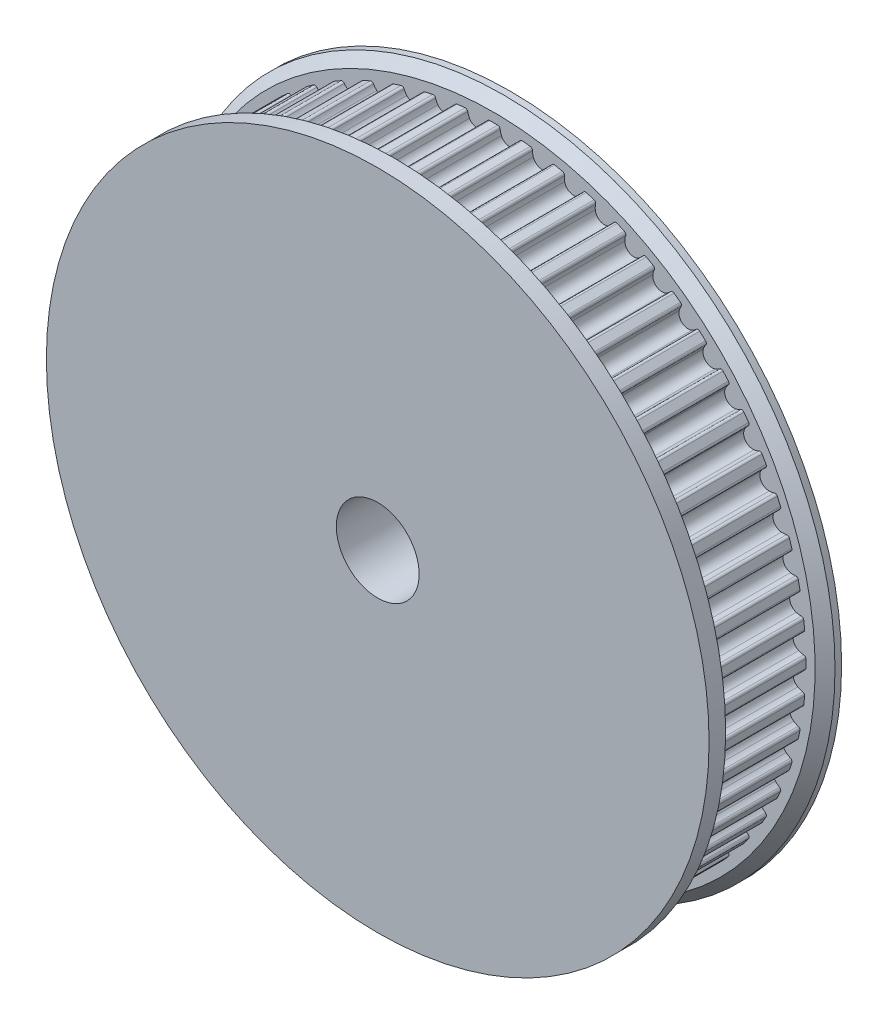
SolidWorks part; units mm, degrees
ref_plane "Front Plane" through (0, 0, 0) normal (0, 0, 1) x (1, 0, 0)
ref_plane "Top Plane" through (0, 0, 0) normal (0, 1, 0) x (1, 0, 0)
ref_plane "Right Plane" through (0, 0, 0) normal (1, 0, 0) x (0, 0, -1)
sketch "Sketch1" plane through (0, 0, 0) normal (0, 0, 1) x (1, 0, 0)
  line L0 (0, 0) -> (0, 19.0986) construction
  line L1 (0, 18.8446) -> (0.2403, 18.8446)
  line L2 (0, 0) -> (0.976, 18.624) construction
  line L3 (0.976, 18.624) -> (0.9995, 19.0724) construction
  line L4 (1.9698, 18.7414) -> (1.7308, 18.7665)
  line L5 (1.9698, 18.7414) -> (2.2088, 18.7162)
  line L6 (3.918, 18.4328) -> (3.6829, 18.4828)
  line L7 (3.918, 18.4328) -> (4.1531, 18.3828)
  line L8 (5.8233, 17.9223) -> (5.5947, 17.9965)
  line L9 (5.8233, 17.9223) -> (6.0519, 17.848)
  line L10 (7.6648, 17.2154) -> (7.4452, 17.3131)
  line L11 (7.6648, 17.2154) -> (7.8844, 17.1176)
  line L12 (9.4223, 16.3199) -> (9.2142, 16.4401)
  line L13 (9.4223, 16.3199) -> (9.6304, 16.1997)
  line L14 (11.0766, 15.2456) -> (10.8821, 15.3869)
  line L15 (11.0766, 15.2456) -> (11.271, 15.1043)
  line L16 (12.6095, 14.0043) -> (12.4309, 14.1651)
  line L17 (12.6095, 14.0043) -> (12.7881, 13.8434)
  line L18 (14.0043, 12.6095) -> (13.8434, 12.7881)
  line L19 (14.0043, 12.6095) -> (14.1651, 12.4309)
  line L20 (15.2456, 11.0766) -> (15.1043, 11.271)
  line L21 (15.2456, 11.0766) -> (15.3869, 10.8821)
  line L22 (16.3199, 9.4223) -> (16.1997, 9.6304)
  line L23 (16.3199, 9.4223) -> (16.4401, 9.2142)
  line L24 (17.2154, 7.6648) -> (17.1176, 7.8844)
  line L25 (17.2154, 7.6648) -> (17.3131, 7.4452)
  line L26 (17.9223, 5.8233) -> (17.848, 6.0519)
  line L27 (17.9223, 5.8233) -> (17.9965, 5.5947)
  line L28 (18.4328, 3.918) -> (18.3828, 4.1531)
  line L29 (18.4328, 3.918) -> (18.4828, 3.6829)
  line L30 (18.7414, 1.9698) -> (18.7162, 2.2088)
  line L31 (18.7414, 1.9698) -> (18.7665, 1.7308)
  line L32 (18.8446, 0) -> (18.8446, 0.2403)
  line L33 (18.8446, 0) -> (18.8446, -0.2403)
  line L34 (18.7414, -1.9698) -> (18.7665, -1.7308)
  line L35 (18.7414, -1.9698) -> (18.7162, -2.2088)
  line L36 (18.4328, -3.918) -> (18.4828, -3.6829)
  line L37 (18.4328, -3.918) -> (18.3828, -4.1531)
  line L38 (17.9223, -5.8233) -> (17.9965, -5.5947)
  line L39 (17.9223, -5.8233) -> (17.848, -6.0519)
  line L40 (17.2154, -7.6648) -> (17.3131, -7.4452)
  line L41 (17.2154, -7.6648) -> (17.1176, -7.8844)
  line L42 (16.3199, -9.4223) -> (16.4401, -9.2142)
  line L43 (16.3199, -9.4223) -> (16.1997, -9.6304)
  line L44 (15.2456, -11.0766) -> (15.3869, -10.8821)
  line L45 (15.2456, -11.0766) -> (15.1043, -11.271)
  line L46 (14.0043, -12.6095) -> (14.1651, -12.4309)
  line L47 (14.0043, -12.6095) -> (13.8434, -12.7881)
  line L48 (12.6095, -14.0043) -> (12.7881, -13.8434)
  line L49 (12.6095, -14.0043) -> (12.4309, -14.1651)
  line L50 (11.0766, -15.2456) -> (11.271, -15.1043)
  line L51 (11.0766, -15.2456) -> (10.8821, -15.3869)
  line L52 (9.4223, -16.3199) -> (9.6304, -16.1997)
  line L53 (9.4223, -16.3199) -> (9.2142, -16.4401)
  line L54 (7.6648, -17.2154) -> (7.8844, -17.1176)
  line L55 (7.6648, -17.2154) -> (7.4452, -17.3131)
  line L56 (5.8233, -17.9223) -> (6.0519, -17.848)
  line L57 (5.8233, -17.9223) -> (5.5947, -17.9965)
  line L58 (3.918, -18.4328) -> (4.1531, -18.3828)
  line L59 (3.918, -18.4328) -> (3.6829, -18.4828)
  line L60 (1.9698, -18.7414) -> (2.2088, -18.7162)
  line L61 (1.9698, -18.7414) -> (1.7308, -18.7665)
  line L62 (0, -18.8446) -> (0.2403, -18.8446)
  line L63 (0, -18.8446) -> (-0.2403, -18.8446)
  line L64 (-1.9698, -18.7414) -> (-1.7308, -18.7665)
  line L65 (-1.9698, -18.7414) -> (-2.2088, -18.7162)
  line L66 (-3.918, -18.4328) -> (-3.6829, -18.4828)
  line L67 (-3.918, -18.4328) -> (-4.1531, -18.3828)
  line L68 (-5.8233, -17.9223) -> (-5.5947, -17.9965)
  line L69 (-5.8233, -17.9223) -> (-6.0519, -17.848)
  line L70 (-7.6648, -17.2154) -> (-7.4452, -17.3131)
  line L71 (-7.6648, -17.2154) -> (-7.8844, -17.1176)
  line L72 (-9.4223, -16.3199) -> (-9.2142, -16.4401)
  line L73 (-9.4223, -16.3199) -> (-9.6304, -16.1997)
  line L74 (-11.0766, -15.2456) -> (-10.8821, -15.3869)
  line L75 (-11.0766, -15.2456) -> (-11.271, -15.1043)
  line L76 (-12.6095, -14.0043) -> (-12.4309, -14.1651)
  line L77 (-12.6095, -14.0043) -> (-12.7881, -13.8434)
  line L78 (-14.0043, -12.6095) -> (-13.8434, -12.7881)
  line L79 (-14.0043, -12.6095) -> (-14.1651, -12.4309)
  line L80 (-15.2456, -11.0766) -> (-15.1043, -11.271)
  line L81 (-15.2456, -11.0766) -> (-15.3869, -10.8821)
  line L82 (-16.3199, -9.4223) -> (-16.1997, -9.6304)
  line L83 (-16.3199, -9.4223) -> (-16.4401, -9.2142)
  line L84 (-17.2154, -7.6648) -> (-17.1176, -7.8844)
  line L85 (-17.2154, -7.6648) -> (-17.3131, -7.4452)
  line L86 (-17.9223, -5.8233) -> (-17.848, -6.0519)
  line L87 (-17.9223, -5.8233) -> (-17.9965, -5.5947)
  line L88 (-18.4328, -3.918) -> (-18.3828, -4.1531)
  line L89 (-18.4328, -3.918) -> (-18.4828, -3.6829)
  line L90 (-18.7414, -1.9698) -> (-18.7162, -2.2088)
  line L91 (-18.7414, -1.9698) -> (-18.7665, -1.7308)
  line L92 (-18.8446, 0) -> (-18.8446, -0.2403)
  line L93 (-18.8446, 0) -> (-18.8446, 0.2403)
  line L94 (-18.7414, 1.9698) -> (-18.7665, 1.7308)
  line L95 (-18.7414, 1.9698) -> (-18.7162, 2.2088)
  line L96 (-18.4328, 3.918) -> (-18.4828, 3.6829)
  line L97 (-18.4328, 3.918) -> (-18.3828, 4.1531)
  line L98 (-17.9223, 5.8233) -> (-17.9965, 5.5947)
  line L99 (-17.9223, 5.8233) -> (-17.848, 6.0519)
  line L100 (-17.2154, 7.6648) -> (-17.3131, 7.4452)
  line L101 (-17.2154, 7.6648) -> (-17.1176, 7.8844)
  line L102 (-16.3199, 9.4223) -> (-16.4401, 9.2142)
  line L103 (-16.3199, 9.4223) -> (-16.1997, 9.6304)
  line L104 (-15.2456, 11.0766) -> (-15.3869, 10.8821)
  line L105 (-15.2456, 11.0766) -> (-15.1043, 11.271)
  line L106 (-14.0043, 12.6095) -> (-14.1651, 12.4309)
  line L107 (-14.0043, 12.6095) -> (-13.8434, 12.7881)
  line L108 (-12.6095, 14.0043) -> (-12.7881, 13.8434)
  line L109 (-12.6095, 14.0043) -> (-12.4309, 14.1651)
  line L110 (-11.0766, 15.2456) -> (-11.271, 15.1043)
  line L111 (-11.0766, 15.2456) -> (-10.8821, 15.3869)
  line L112 (-9.4223, 16.3199) -> (-9.6304, 16.1997)
  line L113 (-9.4223, 16.3199) -> (-9.2142, 16.4401)
  line L114 (-7.6648, 17.2154) -> (-7.8844, 17.1176)
  line L115 (-7.6648, 17.2154) -> (-7.4452, 17.3131)
  line L116 (-5.8233, 17.9223) -> (-6.0519, 17.848)
  line L117 (-5.8233, 17.9223) -> (-5.5947, 17.9965)
  line L118 (-3.918, 18.4328) -> (-4.1531, 18.3828)
  line L119 (-3.918, 18.4328) -> (-3.6829, 18.4828)
  line L120 (-1.9698, 18.7414) -> (-2.2088, 18.7162)
  line L121 (-1.9698, 18.7414) -> (-1.7308, 18.7665)
  line L122 (0, 18.8446) -> (-0.2403, 18.8446)
  line L123 (0, 0) -> (1.4615, 18.3551) construction
  circle A0 centre (0, 0) radius 19.0986 construction
  arc A1 (0.2403, 18.8446) -> (0.3897, 18.7081) centre (0.2403, 18.6946) cw
  arc A2 (0.3897, 18.7081) -> (0.4651, 18.4073) centre (1.3857, 18.7978) ccw
  arc A3 (0.4651, 18.4073) -> (1.4615, 18.3551) centre (0.976, 18.624) ccw
  arc A4 (1.5679, 18.6463) -> (1.4615, 18.3551) centre (0.5868, 18.8397) cw
  arc A5 (1.7308, 18.7665) -> (1.5679, 18.6463) centre (1.7151, 18.6173) ccw
  arc A6 (2.2088, 18.7162) -> (2.3431, 18.5648) centre (2.1931, 18.5671) cw
  arc A7 (2.3431, 18.5648) -> (2.3867, 18.2578) centre (3.343, 18.55) ccw
  arc A8 (2.3867, 18.2578) -> (3.3721, 18.1017) centre (2.9174, 18.42) ccw
  arc A9 (3.5084, 18.3803) -> (3.3721, 18.1017) centre (2.5529, 18.6752) cw
  arc A10 (3.6829, 18.4828) -> (3.5084, 18.3803) centre (3.6517, 18.336) ccw
  arc A11 (4.1531, 18.3828) -> (4.2708, 18.2182) centre (4.1219, 18.2361) cw
  arc A12 (4.2708, 18.2182) -> (4.282, 17.9083) centre (5.2637, 18.099) ccw
  arc A13 (4.282, 17.9083) -> (5.2458, 17.6501) centre (4.8269, 18.0141) ccw
  arc A14 (5.4104, 17.9129) -> (5.2458, 17.6501) centre (4.491, 18.306) cw
  arc A15 (5.5947, 17.9965) -> (5.4104, 17.9129) centre (5.5484, 17.8539) ccw
  arc A16 (6.0519, 17.848) -> (6.1518, 17.672) centre (6.0055, 17.7053) cw
  arc A17 (6.1518, 17.672) -> (6.1305, 17.3626) centre (7.1267, 17.4496) ccw
  arc A18 (6.1305, 17.3626) -> (7.062, 17.0051) centre (6.6834, 17.4109) ccw
  arc A19 (7.2532, 17.2492) -> (7.062, 17.0051) centre (6.3799, 17.7363) cw
  arc A20 (7.4452, 17.3131) -> (7.2532, 17.2492) centre (7.3842, 17.1761) ccw
  arc A21 (7.8844, 17.1176) -> (7.9653, 16.9321) centre (7.8233, 16.9806) cw
  arc A22 (7.9653, 16.9321) -> (7.9118, 16.6267) centre (8.9117, 16.6091) ccw
  arc A23 (7.9118, 16.6267) -> (8.8008, 16.1737) centre (8.4667, 16.6169) ccw
  arc A24 (9.0165, 16.3965) -> (8.8008, 16.1737) centre (8.1989, 16.9723) cw
  arc A25 (9.2142, 16.4401) -> (9.0165, 16.3965) centre (9.1392, 16.3102) ccw
  arc A26 (9.6304, 16.1997) -> (9.6916, 16.0068) centre (9.5554, 16.0698) cw
  arc A27 (9.6916, 16.0068) -> (9.6064, 15.7086) centre (10.599, 15.5866) ccw
  arc A28 (9.6064, 15.7086) -> (10.4432, 15.1652) centre (10.1573, 15.6409) ccw
  arc A29 (10.681, 15.3642) -> (10.4432, 15.1652) centre (9.928, 16.0223) cw
  arc A30 (10.8821, 15.3869) -> (10.681, 15.3642) centre (10.794, 15.2655) ccw
  arc A31 (11.271, 15.1043) -> (11.3116, 14.9061) centre (11.1828, 14.983) cw
  arc A32 (11.3116, 14.9061) -> (11.1958, 14.6184) centre (12.1701, 14.3933) ccw
  arc A33 (11.1958, 14.6184) -> (11.9712, 13.9905) centre (11.7366, 14.4935) ccw
  arc A34 (12.2285, 14.1636) -> (11.9712, 13.9905) centre (11.5484, 14.8967) cw
  arc A35 (12.4309, 14.1651) -> (12.2285, 14.1636) centre (12.3305, 14.0536) ccw
  arc A36 (12.7881, 13.8434) -> (12.8078, 13.642) centre (12.6877, 13.732) cw
  arc A37 (12.8078, 13.642) -> (12.6625, 13.368) centre (13.608, 13.0423) ccw
  arc A38 (12.6625, 13.368) -> (13.368, 12.6625) centre (13.1873, 13.1873) ccw
  arc A39 (13.642, 12.8078) -> (13.368, 12.6625) centre (13.0423, 13.608) cw
  arc A40 (13.8434, 12.7881) -> (13.642, 12.8078) centre (13.732, 12.6877) ccw
  arc A41 (14.1651, 12.4309) -> (14.1636, 12.2285) centre (14.0536, 12.3305) cw
  arc A42 (14.1636, 12.2285) -> (13.9905, 11.9712) centre (14.8967, 11.5484) ccw
  arc A43 (13.9905, 11.9712) -> (14.6184, 11.1958) centre (14.4935, 11.7366) ccw
  arc A44 (14.9061, 11.3116) -> (14.6184, 11.1958) centre (14.3933, 12.1701) cw
  arc A45 (15.1043, 11.271) -> (14.9061, 11.3116) centre (14.983, 11.1828) ccw
  arc A46 (15.3869, 10.8821) -> (15.3642, 10.681) centre (15.2655, 10.794) cw
  arc A47 (15.3642, 10.681) -> (15.1652, 10.4432) centre (16.0223, 9.928) ccw
  arc A48 (15.1652, 10.4432) -> (15.7086, 9.6064) centre (15.6409, 10.1573) ccw
  arc A49 (16.0068, 9.6916) -> (15.7086, 9.6064) centre (15.5866, 10.599) cw
  arc A50 (16.1997, 9.6304) -> (16.0068, 9.6916) centre (16.0698, 9.5554) ccw
  arc A51 (16.4401, 9.2142) -> (16.3965, 9.0165) centre (16.3102, 9.1392) cw
  arc A52 (16.3965, 9.0165) -> (16.1737, 8.8008) centre (16.9723, 8.1989) ccw
  arc A53 (16.1737, 8.8008) -> (16.6267, 7.9118) centre (16.6169, 8.4667) ccw
  arc A54 (16.9321, 7.9653) -> (16.6267, 7.9118) centre (16.6091, 8.9117) cw
  arc A55 (17.1176, 7.8844) -> (16.9321, 7.9653) centre (16.9806, 7.8233) ccw
  arc A56 (17.3131, 7.4452) -> (17.2492, 7.2532) centre (17.1761, 7.3842) cw
  arc A57 (17.2492, 7.2532) -> (17.0051, 7.062) centre (17.7363, 6.3799) ccw
  arc A58 (17.0051, 7.062) -> (17.3626, 6.1305) centre (17.4109, 6.6834) ccw
  arc A59 (17.672, 6.1518) -> (17.3626, 6.1305) centre (17.4496, 7.1267) cw
  arc A60 (17.848, 6.0519) -> (17.672, 6.1518) centre (17.7053, 6.0055) ccw
  arc A61 (17.9965, 5.5947) -> (17.9129, 5.4104) centre (17.8539, 5.5484) cw
  arc A62 (17.9129, 5.4104) -> (17.6501, 5.2458) centre (18.306, 4.491) ccw
  arc A63 (17.6501, 5.2458) -> (17.9083, 4.282) centre (18.0141, 4.8269) ccw
  arc A64 (18.2182, 4.2708) -> (17.9083, 4.282) centre (18.099, 5.2637) cw
  arc A65 (18.3828, 4.1531) -> (18.2182, 4.2708) centre (18.2361, 4.1219) ccw
  arc A66 (18.4828, 3.6829) -> (18.3803, 3.5084) centre (18.336, 3.6517) cw
  arc A67 (18.3803, 3.5084) -> (18.1017, 3.3721) centre (18.6752, 2.5529) ccw
  arc A68 (18.1017, 3.3721) -> (18.2578, 2.3867) centre (18.42, 2.9174) ccw
  arc A69 (18.5648, 2.3431) -> (18.2578, 2.3867) centre (18.55, 3.343) cw
  arc A70 (18.7162, 2.2088) -> (18.5648, 2.3431) centre (18.5671, 2.1931) ccw
  arc A71 (18.7665, 1.7308) -> (18.6463, 1.5679) centre (18.6173, 1.7151) cw
  arc A72 (18.6463, 1.5679) -> (18.3551, 1.4615) centre (18.8397, 0.5868) ccw
  arc A73 (18.3551, 1.4615) -> (18.4073, 0.4651) centre (18.624, 0.976) ccw
  arc A74 (18.7081, 0.3897) -> (18.4073, 0.4651) centre (18.7978, 1.3857) cw
  arc A75 (18.8446, 0.2403) -> (18.7081, 0.3897) centre (18.6946, 0.2403) ccw
  arc A76 (18.8446, -0.2403) -> (18.7081, -0.3897) centre (18.6946, -0.2403) cw
  arc A77 (18.7081, -0.3897) -> (18.4073, -0.4651) centre (18.7978, -1.3857) ccw
  arc A78 (18.4073, -0.4651) -> (18.3551, -1.4615) centre (18.624, -0.976) ccw
  arc A79 (18.6463, -1.5679) -> (18.3551, -1.4615) centre (18.8397, -0.5868) cw
  arc A80 (18.7665, -1.7308) -> (18.6463, -1.5679) centre (18.6173, -1.7151) ccw
  arc A81 (18.7162, -2.2088) -> (18.5648, -2.3431) centre (18.5671, -2.1931) cw
  arc A82 (18.5648, -2.3431) -> (18.2578, -2.3867) centre (18.55, -3.343) ccw
  arc A83 (18.2578, -2.3867) -> (18.1017, -3.3721) centre (18.42, -2.9174) ccw
  arc A84 (18.3803, -3.5084) -> (18.1017, -3.3721) centre (18.6752, -2.5529) cw
  arc A85 (18.4828, -3.6829) -> (18.3803, -3.5084) centre (18.336, -3.6517) ccw
  arc A86 (18.3828, -4.1531) -> (18.2182, -4.2708) centre (18.2361, -4.1219) cw
  arc A87 (18.2182, -4.2708) -> (17.9083, -4.282) centre (18.099, -5.2637) ccw
  arc A88 (17.9083, -4.282) -> (17.6501, -5.2458) centre (18.0141, -4.8269) ccw
  arc A89 (17.9129, -5.4104) -> (17.6501, -5.2458) centre (18.306, -4.491) cw
  arc A90 (17.9965, -5.5947) -> (17.9129, -5.4104) centre (17.8539, -5.5484) ccw
  arc A91 (17.848, -6.0519) -> (17.672, -6.1518) centre (17.7053, -6.0055) cw
  arc A92 (17.672, -6.1518) -> (17.3626, -6.1305) centre (17.4496, -7.1267) ccw
  arc A93 (17.3626, -6.1305) -> (17.0051, -7.062) centre (17.4109, -6.6834) ccw
  arc A94 (17.2492, -7.2532) -> (17.0051, -7.062) centre (17.7363, -6.3799) cw
  arc A95 (17.3131, -7.4452) -> (17.2492, -7.2532) centre (17.1761, -7.3842) ccw
  arc A96 (17.1176, -7.8844) -> (16.9321, -7.9653) centre (16.9806, -7.8233) cw
  arc A97 (16.9321, -7.9653) -> (16.6267, -7.9118) centre (16.6091, -8.9117) ccw
  arc A98 (16.6267, -7.9118) -> (16.1737, -8.8008) centre (16.6169, -8.4667) ccw
  arc A99 (16.3965, -9.0165) -> (16.1737, -8.8008) centre (16.9723, -8.1989) cw
  arc A100 (16.4401, -9.2142) -> (16.3965, -9.0165) centre (16.3102, -9.1392) ccw
  arc A101 (16.1997, -9.6304) -> (16.0068, -9.6916) centre (16.0698, -9.5554) cw
  arc A102 (16.0068, -9.6916) -> (15.7086, -9.6064) centre (15.5866, -10.599) ccw
  arc A103 (15.7086, -9.6064) -> (15.1652, -10.4432) centre (15.6409, -10.1573) ccw
  arc A104 (15.3642, -10.681) -> (15.1652, -10.4432) centre (16.0223, -9.928) cw
  arc A105 (15.3869, -10.8821) -> (15.3642, -10.681) centre (15.2655, -10.794) ccw
  arc A106 (15.1043, -11.271) -> (14.9061, -11.3116) centre (14.983, -11.1828) cw
  arc A107 (14.9061, -11.3116) -> (14.6184, -11.1958) centre (14.3933, -12.1701) ccw
  arc A108 (14.6184, -11.1958) -> (13.9905, -11.9712) centre (14.4935, -11.7366) ccw
  arc A109 (14.1636, -12.2285) -> (13.9905, -11.9712) centre (14.8967, -11.5484) cw
  arc A110 (14.1651, -12.4309) -> (14.1636, -12.2285) centre (14.0536, -12.3305) ccw
  arc A111 (13.8434, -12.7881) -> (13.642, -12.8078) centre (13.732, -12.6877) cw
  arc A112 (13.642, -12.8078) -> (13.368, -12.6625) centre (13.0423, -13.608) ccw
  arc A113 (13.368, -12.6625) -> (12.6625, -13.368) centre (13.1873, -13.1873) ccw
  arc A114 (12.8078, -13.642) -> (12.6625, -13.368) centre (13.608, -13.0423) cw
  arc A115 (12.7881, -13.8434) -> (12.8078, -13.642) centre (12.6877, -13.732) ccw
  arc A116 (12.4309, -14.1651) -> (12.2285, -14.1636) centre (12.3305, -14.0536) cw
  arc A117 (12.2285, -14.1636) -> (11.9712, -13.9905) centre (11.5484, -14.8967) ccw
  arc A118 (11.9712, -13.9905) -> (11.1958, -14.6184) centre (11.7366, -14.4935) ccw
  arc A119 (11.3116, -14.9061) -> (11.1958, -14.6184) centre (12.1701, -14.3933) cw
  arc A120 (11.271, -15.1043) -> (11.3116, -14.9061) centre (11.1828, -14.983) ccw
  arc A121 (10.8821, -15.3869) -> (10.681, -15.3642) centre (10.794, -15.2655) cw
  arc A122 (10.681, -15.3642) -> (10.4432, -15.1652) centre (9.928, -16.0223) ccw
  arc A123 (10.4432, -15.1652) -> (9.6064, -15.7086) centre (10.1573, -15.6409) ccw
  arc A124 (9.6916, -16.0068) -> (9.6064, -15.7086) centre (10.599, -15.5866) cw
  arc A125 (9.6304, -16.1997) -> (9.6916, -16.0068) centre (9.5554, -16.0698) ccw
  arc A126 (9.2142, -16.4401) -> (9.0165, -16.3965) centre (9.1392, -16.3102) cw
  arc A127 (9.0165, -16.3965) -> (8.8008, -16.1737) centre (8.1989, -16.9723) ccw
  arc A128 (8.8008, -16.1737) -> (7.9118, -16.6267) centre (8.4667, -16.6169) ccw
  arc A129 (7.9653, -16.9321) -> (7.9118, -16.6267) centre (8.9117, -16.6091) cw
  arc A130 (7.8844, -17.1176) -> (7.9653, -16.9321) centre (7.8233, -16.9806) ccw
  arc A131 (7.4452, -17.3131) -> (7.2532, -17.2492) centre (7.3842, -17.1761) cw
  arc A132 (7.2532, -17.2492) -> (7.062, -17.0051) centre (6.3799, -17.7363) ccw
  arc A133 (7.062, -17.0051) -> (6.1305, -17.3626) centre (6.6834, -17.4109) ccw
  arc A134 (6.1518, -17.672) -> (6.1305, -17.3626) centre (7.1267, -17.4496) cw
  arc A135 (6.0519, -17.848) -> (6.1518, -17.672) centre (6.0055, -17.7053) ccw
  arc A136 (5.5947, -17.9965) -> (5.4104, -17.9129) centre (5.5484, -17.8539) cw
  arc A137 (5.4104, -17.9129) -> (5.2458, -17.6501) centre (4.491, -18.306) ccw
  arc A138 (5.2458, -17.6501) -> (4.282, -17.9083) centre (4.8269, -18.0141) ccw
  arc A139 (4.2708, -18.2182) -> (4.282, -17.9083) centre (5.2637, -18.099) cw
  arc A140 (4.1531, -18.3828) -> (4.2708, -18.2182) centre (4.1219, -18.2361) ccw
  arc A141 (3.6829, -18.4828) -> (3.5084, -18.3803) centre (3.6517, -18.336) cw
  arc A142 (3.5084, -18.3803) -> (3.3721, -18.1017) centre (2.5529, -18.6752) ccw
  arc A143 (3.3721, -18.1017) -> (2.3867, -18.2578) centre (2.9174, -18.42) ccw
  arc A144 (2.3431, -18.5648) -> (2.3867, -18.2578) centre (3.343, -18.55) cw
  arc A145 (2.2088, -18.7162) -> (2.3431, -18.5648) centre (2.1931, -18.5671) ccw
  arc A146 (1.7308, -18.7665) -> (1.5679, -18.6463) centre (1.7151, -18.6173) cw
  arc A147 (1.5679, -18.6463) -> (1.4615, -18.3551) centre (0.5868, -18.8397) ccw
  arc A148 (1.4615, -18.3551) -> (0.4651, -18.4073) centre (0.976, -18.624) ccw
  arc A149 (0.3897, -18.7081) -> (0.4651, -18.4073) centre (1.3857, -18.7978) cw
  arc A150 (0.2403, -18.8446) -> (0.3897, -18.7081) centre (0.2403, -18.6946) ccw
  arc A151 (-0.2403, -18.8446) -> (-0.3897, -18.7081) centre (-0.2403, -18.6946) cw
  arc A152 (-0.3897, -18.7081) -> (-0.4651, -18.4073) centre (-1.3857, -18.7978) ccw
  arc A153 (-0.4651, -18.4073) -> (-1.4615, -18.3551) centre (-0.976, -18.624) ccw
  arc A154 (-1.5679, -18.6463) -> (-1.4615, -18.3551) centre (-0.5868, -18.8397) cw
  arc A155 (-1.7308, -18.7665) -> (-1.5679, -18.6463) centre (-1.7151, -18.6173) ccw
  arc A156 (-2.2088, -18.7162) -> (-2.3431, -18.5648) centre (-2.1931, -18.5671) cw
  arc A157 (-2.3431, -18.5648) -> (-2.3867, -18.2578) centre (-3.343, -18.55) ccw
  arc A158 (-2.3867, -18.2578) -> (-3.3721, -18.1017) centre (-2.9174, -18.42) ccw
  arc A159 (-3.5084, -18.3803) -> (-3.3721, -18.1017) centre (-2.5529, -18.6752) cw
  arc A160 (-3.6829, -18.4828) -> (-3.5084, -18.3803) centre (-3.6517, -18.336) ccw
  arc A161 (-4.1531, -18.3828) -> (-4.2708, -18.2182) centre (-4.1219, -18.2361) cw
  arc A162 (-4.2708, -18.2182) -> (-4.282, -17.9083) centre (-5.2637, -18.099) ccw
  arc A163 (-4.282, -17.9083) -> (-5.2458, -17.6501) centre (-4.8269, -18.0141) ccw
  arc A164 (-5.4104, -17.9129) -> (-5.2458, -17.6501) centre (-4.491, -18.306) cw
  arc A165 (-5.5947, -17.9965) -> (-5.4104, -17.9129) centre (-5.5484, -17.8539) ccw
  arc A166 (-6.0519, -17.848) -> (-6.1518, -17.672) centre (-6.0055, -17.7053) cw
  arc A167 (-6.1518, -17.672) -> (-6.1305, -17.3626) centre (-7.1267, -17.4496) ccw
  arc A168 (-6.1305, -17.3626) -> (-7.062, -17.0051) centre (-6.6834, -17.4109) ccw
  arc A169 (-7.2532, -17.2492) -> (-7.062, -17.0051) centre (-6.3799, -17.7363) cw
  arc A170 (-7.4452, -17.3131) -> (-7.2532, -17.2492) centre (-7.3842, -17.1761) ccw
  arc A171 (-7.8844, -17.1176) -> (-7.9653, -16.9321) centre (-7.8233, -16.9806) cw
  arc A172 (-7.9653, -16.9321) -> (-7.9118, -16.6267) centre (-8.9117, -16.6091) ccw
  arc A173 (-7.9118, -16.6267) -> (-8.8008, -16.1737) centre (-8.4667, -16.6169) ccw
  arc A174 (-9.0165, -16.3965) -> (-8.8008, -16.1737) centre (-8.1989, -16.9723) cw
  arc A175 (-9.2142, -16.4401) -> (-9.0165, -16.3965) centre (-9.1392, -16.3102) ccw
  arc A176 (-9.6304, -16.1997) -> (-9.6916, -16.0068) centre (-9.5554, -16.0698) cw
  arc A177 (-9.6916, -16.0068) -> (-9.6064, -15.7086) centre (-10.599, -15.5866) ccw
  arc A178 (-9.6064, -15.7086) -> (-10.4432, -15.1652) centre (-10.1573, -15.6409) ccw
  arc A179 (-10.681, -15.3642) -> (-10.4432, -15.1652) centre (-9.928, -16.0223) cw
  arc A180 (-10.8821, -15.3869) -> (-10.681, -15.3642) centre (-10.794, -15.2655) ccw
  arc A181 (-11.271, -15.1043) -> (-11.3116, -14.9061) centre (-11.1828, -14.983) cw
  arc A182 (-11.3116, -14.9061) -> (-11.1958, -14.6184) centre (-12.1701, -14.3933) ccw
  arc A183 (-11.1958, -14.6184) -> (-11.9712, -13.9905) centre (-11.7366, -14.4935) ccw
  arc A184 (-12.2285, -14.1636) -> (-11.9712, -13.9905) centre (-11.5484, -14.8967) cw
  arc A185 (-12.4309, -14.1651) -> (-12.2285, -14.1636) centre (-12.3305, -14.0536) ccw
  arc A186 (-12.7881, -13.8434) -> (-12.8078, -13.642) centre (-12.6877, -13.732) cw
  arc A187 (-12.8078, -13.642) -> (-12.6625, -13.368) centre (-13.608, -13.0423) ccw
  arc A188 (-12.6625, -13.368) -> (-13.368, -12.6625) centre (-13.1873, -13.1873) ccw
  arc A189 (-13.642, -12.8078) -> (-13.368, -12.6625) centre (-13.0423, -13.608) cw
  arc A190 (-13.8434, -12.7881) -> (-13.642, -12.8078) centre (-13.732, -12.6877) ccw
  arc A191 (-14.1651, -12.4309) -> (-14.1636, -12.2285) centre (-14.0536, -12.3305) cw
  arc A192 (-14.1636, -12.2285) -> (-13.9905, -11.9712) centre (-14.8967, -11.5484) ccw
  arc A193 (-13.9905, -11.9712) -> (-14.6184, -11.1958) centre (-14.4935, -11.7366) ccw
  arc A194 (-14.9061, -11.3116) -> (-14.6184, -11.1958) centre (-14.3933, -12.1701) cw
  arc A195 (-15.1043, -11.271) -> (-14.9061, -11.3116) centre (-14.983, -11.1828) ccw
  arc A196 (-15.3869, -10.8821) -> (-15.3642, -10.681) centre (-15.2655, -10.794) cw
  arc A197 (-15.3642, -10.681) -> (-15.1652, -10.4432) centre (-16.0223, -9.928) ccw
  arc A198 (-15.1652, -10.4432) -> (-15.7086, -9.6064) centre (-15.6409, -10.1573) ccw
  arc A199 (-16.0068, -9.6916) -> (-15.7086, -9.6064) centre (-15.5866, -10.599) cw
  arc A200 (-16.1997, -9.6304) -> (-16.0068, -9.6916) centre (-16.0698, -9.5554) ccw
  arc A201 (-16.4401, -9.2142) -> (-16.3965, -9.0165) centre (-16.3102, -9.1392) cw
  arc A202 (-16.3965, -9.0165) -> (-16.1737, -8.8008) centre (-16.9723, -8.1989) ccw
  arc A203 (-16.1737, -8.8008) -> (-16.6267, -7.9118) centre (-16.6169, -8.4667) ccw
  arc A204 (-16.9321, -7.9653) -> (-16.6267, -7.9118) centre (-16.6091, -8.9117) cw
  arc A205 (-17.1176, -7.8844) -> (-16.9321, -7.9653) centre (-16.9806, -7.8233) ccw
  arc A206 (-17.3131, -7.4452) -> (-17.2492, -7.2532) centre (-17.1761, -7.3842) cw
  arc A207 (-17.2492, -7.2532) -> (-17.0051, -7.062) centre (-17.7363, -6.3799) ccw
  arc A208 (-17.0051, -7.062) -> (-17.3626, -6.1305) centre (-17.4109, -6.6834) ccw
  arc A209 (-17.672, -6.1518) -> (-17.3626, -6.1305) centre (-17.4496, -7.1267) cw
  arc A210 (-17.848, -6.0519) -> (-17.672, -6.1518) centre (-17.7053, -6.0055) ccw
  arc A211 (-17.9965, -5.5947) -> (-17.9129, -5.4104) centre (-17.8539, -5.5484) cw
  arc A212 (-17.9129, -5.4104) -> (-17.6501, -5.2458) centre (-18.306, -4.491) ccw
  arc A213 (-17.6501, -5.2458) -> (-17.9083, -4.282) centre (-18.0141, -4.8269) ccw
  arc A214 (-18.2182, -4.2708) -> (-17.9083, -4.282) centre (-18.099, -5.2637) cw
  arc A215 (-18.3828, -4.1531) -> (-18.2182, -4.2708) centre (-18.2361, -4.1219) ccw
  arc A216 (-18.4828, -3.6829) -> (-18.3803, -3.5084) centre (-18.336, -3.6517) cw
  arc A217 (-18.3803, -3.5084) -> (-18.1017, -3.3721) centre (-18.6752, -2.5529) ccw
  arc A218 (-18.1017, -3.3721) -> (-18.2578, -2.3867) centre (-18.42, -2.9174) ccw
  arc A219 (-18.5648, -2.3431) -> (-18.2578, -2.3867) centre (-18.55, -3.343) cw
  arc A220 (-18.7162, -2.2088) -> (-18.5648, -2.3431) centre (-18.5671, -2.1931) ccw
  arc A221 (-18.7665, -1.7308) -> (-18.6463, -1.5679) centre (-18.6173, -1.7151) cw
  arc A222 (-18.6463, -1.5679) -> (-18.3551, -1.4615) centre (-18.8397, -0.5868) ccw
  arc A223 (-18.3551, -1.4615) -> (-18.4073, -0.4651) centre (-18.624, -0.976) ccw
  arc A224 (-18.7081, -0.3897) -> (-18.4073, -0.4651) centre (-18.7978, -1.3857) cw
  arc A225 (-18.8446, -0.2403) -> (-18.7081, -0.3897) centre (-18.6946, -0.2403) ccw
  arc A226 (-18.8446, 0.2403) -> (-18.7081, 0.3897) centre (-18.6946, 0.2403) cw
  arc A227 (-18.7081, 0.3897) -> (-18.4073, 0.4651) centre (-18.7978, 1.3857) ccw
  arc A228 (-18.4073, 0.4651) -> (-18.3551, 1.4615) centre (-18.624, 0.976) ccw
  arc A229 (-18.6463, 1.5679) -> (-18.3551, 1.4615) centre (-18.8397, 0.5868) cw
  arc A230 (-18.7665, 1.7308) -> (-18.6463, 1.5679) centre (-18.6173, 1.7151) ccw
  arc A231 (-18.7162, 2.2088) -> (-18.5648, 2.3431) centre (-18.5671, 2.1931) cw
  arc A232 (-18.5648, 2.3431) -> (-18.2578, 2.3867) centre (-18.55, 3.343) ccw
  arc A233 (-18.2578, 2.3867) -> (-18.1017, 3.3721) centre (-18.42, 2.9174) ccw
  arc A234 (-18.3803, 3.5084) -> (-18.1017, 3.3721) centre (-18.6752, 2.5529) cw
  arc A235 (-18.4828, 3.6829) -> (-18.3803, 3.5084) centre (-18.336, 3.6517) ccw
  arc A236 (-18.3828, 4.1531) -> (-18.2182, 4.2708) centre (-18.2361, 4.1219) cw
  arc A237 (-18.2182, 4.2708) -> (-17.9083, 4.282) centre (-18.099, 5.2637) ccw
  arc A238 (-17.9083, 4.282) -> (-17.6501, 5.2458) centre (-18.0141, 4.8269) ccw
  arc A239 (-17.9129, 5.4104) -> (-17.6501, 5.2458) centre (-18.306, 4.491) cw
  arc A240 (-17.9965, 5.5947) -> (-17.9129, 5.4104) centre (-17.8539, 5.5484) ccw
  arc A241 (-17.848, 6.0519) -> (-17.672, 6.1518) centre (-17.7053, 6.0055) cw
  arc A242 (-17.672, 6.1518) -> (-17.3626, 6.1305) centre (-17.4496, 7.1267) ccw
  arc A243 (-17.3626, 6.1305) -> (-17.0051, 7.062) centre (-17.4109, 6.6834) ccw
  arc A244 (-17.2492, 7.2532) -> (-17.0051, 7.062) centre (-17.7363, 6.3799) cw
  arc A245 (-17.3131, 7.4452) -> (-17.2492, 7.2532) centre (-17.1761, 7.3842) ccw
  arc A246 (-17.1176, 7.8844) -> (-16.9321, 7.9653) centre (-16.9806, 7.8233) cw
  arc A247 (-16.9321, 7.9653) -> (-16.6267, 7.9118) centre (-16.6091, 8.9117) ccw
  arc A248 (-16.6267, 7.9118) -> (-16.1737, 8.8008) centre (-16.6169, 8.4667) ccw
  arc A249 (-16.3965, 9.0165) -> (-16.1737, 8.8008) centre (-16.9723, 8.1989) cw
  arc A250 (-16.4401, 9.2142) -> (-16.3965, 9.0165) centre (-16.3102, 9.1392) ccw
  arc A251 (-16.1997, 9.6304) -> (-16.0068, 9.6916) centre (-16.0698, 9.5554) cw
  arc A252 (-16.0068, 9.6916) -> (-15.7086, 9.6064) centre (-15.5866, 10.599) ccw
  arc A253 (-15.7086, 9.6064) -> (-15.1652, 10.4432) centre (-15.6409, 10.1573) ccw
  arc A254 (-15.3642, 10.681) -> (-15.1652, 10.4432) centre (-16.0223, 9.928) cw
  arc A255 (-15.3869, 10.8821) -> (-15.3642, 10.681) centre (-15.2655, 10.794) ccw
  arc A256 (-15.1043, 11.271) -> (-14.9061, 11.3116) centre (-14.983, 11.1828) cw
  arc A257 (-14.9061, 11.3116) -> (-14.6184, 11.1958) centre (-14.3933, 12.1701) ccw
  arc A258 (-14.6184, 11.1958) -> (-13.9905, 11.9712) centre (-14.4935, 11.7366) ccw
  arc A259 (-14.1636, 12.2285) -> (-13.9905, 11.9712) centre (-14.8967, 11.5484) cw
  arc A260 (-14.1651, 12.4309) -> (-14.1636, 12.2285) centre (-14.0536, 12.3305) ccw
  arc A261 (-13.8434, 12.7881) -> (-13.642, 12.8078) centre (-13.732, 12.6877) cw
  arc A262 (-13.642, 12.8078) -> (-13.368, 12.6625) centre (-13.0423, 13.608) ccw
  arc A263 (-13.368, 12.6625) -> (-12.6625, 13.368) centre (-13.1873, 13.1873) ccw
  arc A264 (-12.8078, 13.642) -> (-12.6625, 13.368) centre (-13.608, 13.0423) cw
  arc A265 (-12.7881, 13.8434) -> (-12.8078, 13.642) centre (-12.6877, 13.732) ccw
  arc A266 (-12.4309, 14.1651) -> (-12.2285, 14.1636) centre (-12.3305, 14.0536) cw
  arc A267 (-12.2285, 14.1636) -> (-11.9712, 13.9905) centre (-11.5484, 14.8967) ccw
  arc A268 (-11.9712, 13.9905) -> (-11.1958, 14.6184) centre (-11.7366, 14.4935) ccw
  arc A269 (-11.3116, 14.9061) -> (-11.1958, 14.6184) centre (-12.1701, 14.3933) cw
  arc A270 (-11.271, 15.1043) -> (-11.3116, 14.9061) centre (-11.1828, 14.983) ccw
  arc A271 (-10.8821, 15.3869) -> (-10.681, 15.3642) centre (-10.794, 15.2655) cw
  arc A272 (-10.681, 15.3642) -> (-10.4432, 15.1652) centre (-9.928, 16.0223) ccw
  arc A273 (-10.4432, 15.1652) -> (-9.6064, 15.7086) centre (-10.1573, 15.6409) ccw
  arc A274 (-9.6916, 16.0068) -> (-9.6064, 15.7086) centre (-10.599, 15.5866) cw
  arc A275 (-9.6304, 16.1997) -> (-9.6916, 16.0068) centre (-9.5554, 16.0698) ccw
  arc A276 (-9.2142, 16.4401) -> (-9.0165, 16.3965) centre (-9.1392, 16.3102) cw
  arc A277 (-9.0165, 16.3965) -> (-8.8008, 16.1737) centre (-8.1989, 16.9723) ccw
  arc A278 (-8.8008, 16.1737) -> (-7.9118, 16.6267) centre (-8.4667, 16.6169) ccw
  arc A279 (-7.9653, 16.9321) -> (-7.9118, 16.6267) centre (-8.9117, 16.6091) cw
  arc A280 (-7.8844, 17.1176) -> (-7.9653, 16.9321) centre (-7.8233, 16.9806) ccw
  arc A281 (-7.4452, 17.3131) -> (-7.2532, 17.2492) centre (-7.3842, 17.1761) cw
  arc A282 (-7.2532, 17.2492) -> (-7.062, 17.0051) centre (-6.3799, 17.7363) ccw
  arc A283 (-7.062, 17.0051) -> (-6.1305, 17.3626) centre (-6.6834, 17.4109) ccw
  arc A284 (-6.1518, 17.672) -> (-6.1305, 17.3626) centre (-7.1267, 17.4496) cw
  arc A285 (-6.0519, 17.848) -> (-6.1518, 17.672) centre (-6.0055, 17.7053) ccw
  arc A286 (-5.5947, 17.9965) -> (-5.4104, 17.9129) centre (-5.5484, 17.8539) cw
  arc A287 (-5.4104, 17.9129) -> (-5.2458, 17.6501) centre (-4.491, 18.306) ccw
  arc A288 (-5.2458, 17.6501) -> (-4.282, 17.9083) centre (-4.8269, 18.0141) ccw
  arc A289 (-4.2708, 18.2182) -> (-4.282, 17.9083) centre (-5.2637, 18.099) cw
  arc A290 (-4.1531, 18.3828) -> (-4.2708, 18.2182) centre (-4.1219, 18.2361) ccw
  arc A291 (-3.6829, 18.4828) -> (-3.5084, 18.3803) centre (-3.6517, 18.336) cw
  arc A292 (-3.5084, 18.3803) -> (-3.3721, 18.1017) centre (-2.5529, 18.6752) ccw
  arc A293 (-3.3721, 18.1017) -> (-2.3867, 18.2578) centre (-2.9174, 18.42) ccw
  arc A294 (-2.3431, 18.5648) -> (-2.3867, 18.2578) centre (-3.343, 18.55) cw
  arc A295 (-2.2088, 18.7162) -> (-2.3431, 18.5648) centre (-2.1931, 18.5671) ccw
  arc A296 (-1.7308, 18.7665) -> (-1.5679, 18.6463) centre (-1.7151, 18.6173) cw
  arc A297 (-1.5679, 18.6463) -> (-1.4615, 18.3551) centre (-0.5868, 18.8397) ccw
  arc A298 (-1.4615, 18.3551) -> (-0.4651, 18.4073) centre (-0.976, 18.624) ccw
  arc A299 (-0.3897, 18.7081) -> (-0.4651, 18.4073) centre (-1.3857, 18.7978) cw
  arc A300 (-0.2403, 18.8446) -> (-0.3897, 18.7081) centre (-0.2403, 18.6946) ccw
  dimension "D1" = 38.1972
  dimension "D2" = 0.555
  dimension "D3" = 1
  dimension "D4" = 0.15
  dimension "D5" = 0.4
  dimension "D6" = 0.254
  dimension "D7" = 3
  dimension "D9" = 18.4132
  dimension "D8" = 60
extrude "Boss-Extrude1" add sketch "Sketch1" along normal mid plane 6
sketch "Sketch2" plane through (0, 0, -3) normal (0, 0, -1) x (-1, 0, 0)
  circle A0 centre (0, 0) radius 20
  dimension "D1" = 40
extrude "Boss-Extrude2" add sketch "Sketch2" along normal blind 1
sketch "Sketch3" plane through (0, 0, 3) normal (0, 0, 1) x (1, 0, 0)
  circle A0 centre (0, 0) radius 20
extrude "Boss-Extrude3" add sketch "Sketch3" along normal blind 1
sketch "Sketch7" plane through (0, 0, -4) normal (0, 0, -1) x (-1, 0, 0)
  circle A0 centre (0, 0) radius 10
  circle A1 centre (0, 0) radius 6.6
  dimension "D1" = 13.2
  dimension "D2" = 20
extrude "Boss-Extrude4" add sketch "Sketch7" along normal blind 7
sketch "Sketch8" plane through (0, 0, 0) normal (0, 1, 0) x (1, 0, 0)
  line L0 (0, 11) -> (0, 0) construction
  line L1 (10, 11) -> (-10, 11) construction
  circle A0 centre (0, 8) radius 1.75
  dimension "D1" = 3.5
  dimension "D2" = 3
extrude "Cut-Extrude4" cut sketch "Sketch8" against normal through all
pattern_circular "CirPattern2" count 2 every 90 about axis through (0, 0, -11) along (0, 0, 1) of "Cut-Extrude4"
sketch "Sketch9" plane through (0, 0, -4) normal (0, 0, -1) x (-1, 0, 0)
  circle A0 centre (0, 0) radius 2.5
  dimension "D1" = 5
extrude "Cut-Extrude5" cut sketch "Sketch9" against normal through all
fillet "Fillet1" radius 2 1 edges at (-10, 0, -4)
fillet "Fillet2" radius 0.8 1 edges at (-10, 0, -11)
chamfer "Chamfer1" distance 0.6 angle 45 1 edges at (-20, 0, -3)
equation "\"n\"= 60"
equation "\"p\"= 2mm"
equation "\"pd\"= \"n\" * \"p\" / pi"
equation "\"D1@Sketch1\"=\"pd\""
equation "\"D7@Sketch1\"=180/\"n\""
